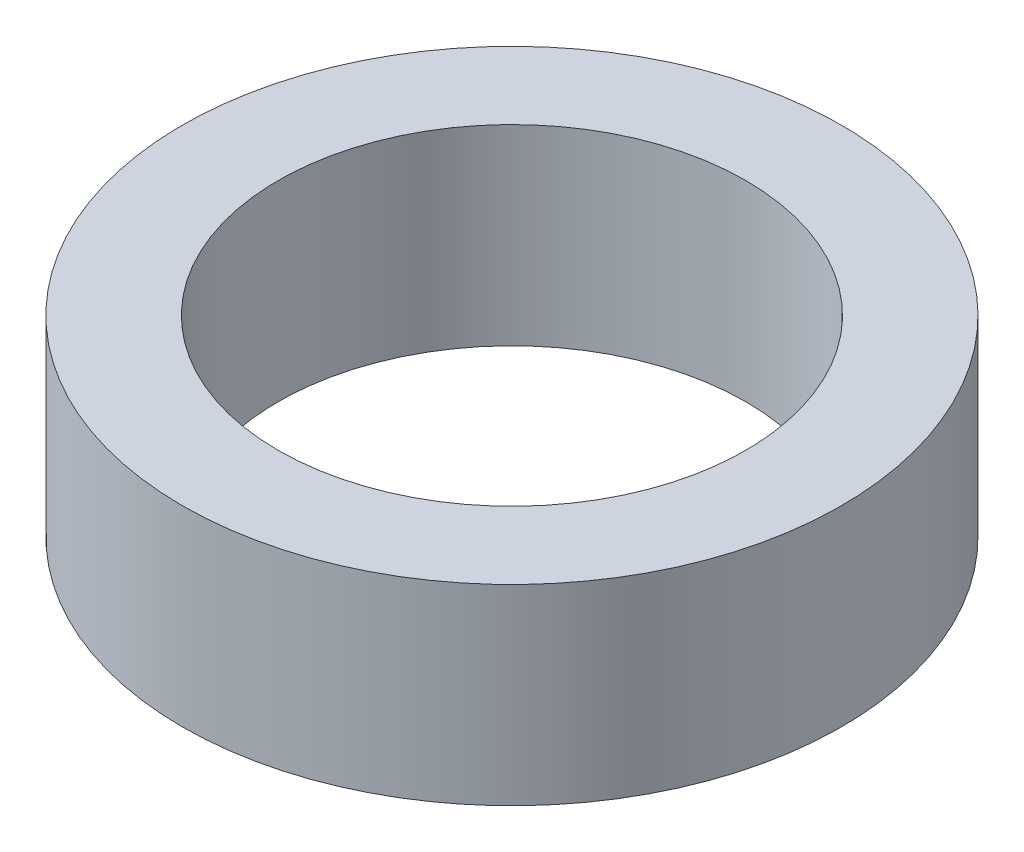
SolidWorks part; units mm, degrees
ref_plane "Front Plane" through (0, 0, 0) normal (0, 0, 1) x (1, 0, 0)
ref_plane "Top Plane" through (0, 0, 0) normal (0, 1, 0) x (1, 0, 0)
ref_plane "Right Plane" through (0, 0, 0) normal (1, 0, 0) x (0, 0, -1)
sketch "Sketch1" plane through (0, 0, 0) normal (0, 1, 0) x (1, 0, 0)
  circle A0 centre (0, 0) radius 6.1
  circle A1 centre (0, 0) radius 8.6
  dimension "D1" = 12.2
  dimension "D2" = 2.5
extrude "Boss-Extrude1" add sketch "Sketch1" along normal blind 5
